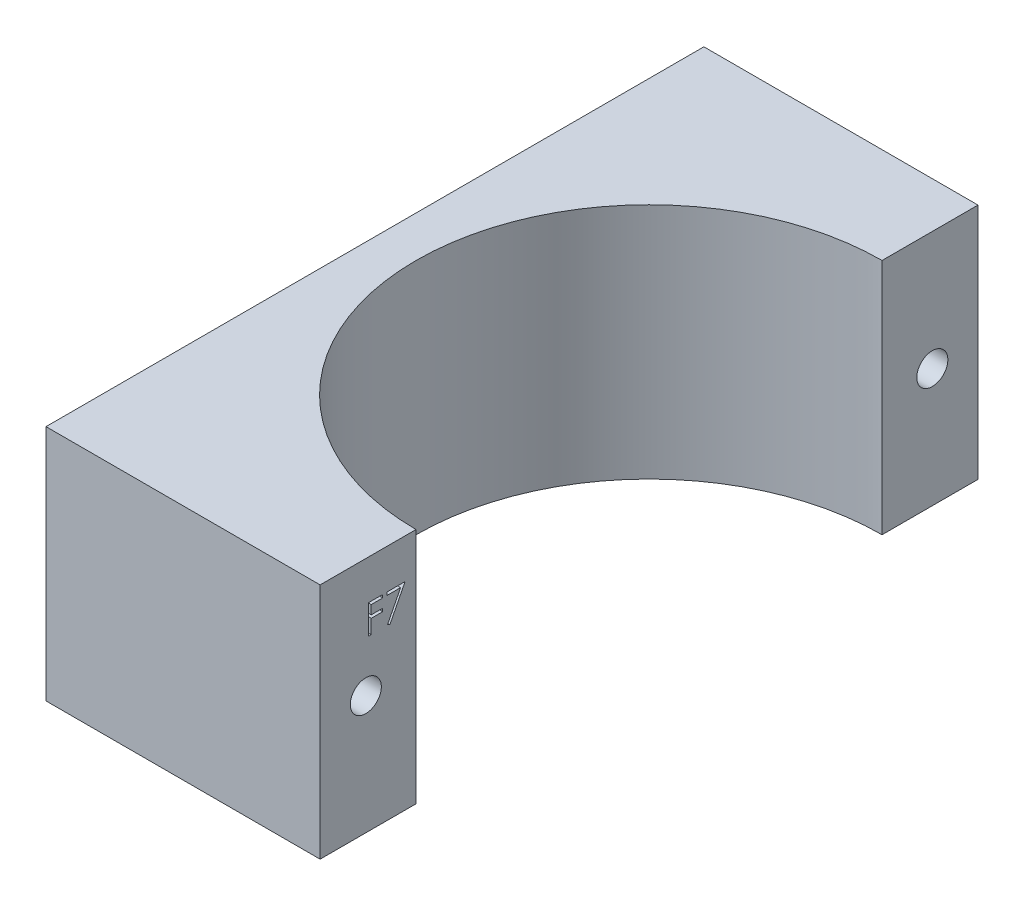
SolidWorks part; units mm, degrees
ref_plane "Front Plane" through (0, 0, 0) normal (0, 0, 1) x (1, 0, 0)
ref_plane "Top Plane" through (0, 0, 0) normal (0, 1, 0) x (1, 0, 0)
ref_plane "Right Plane" through (0, 0, 0) normal (1, 0, 0) x (0, 0, -1)
sketch "Sketch1" plane through (0, 0, 0) normal (0, 1, 0) x (1, 0, 0)
  line L0 (-46.9983, 32.5286) -> (-46.9983, -39.4714)
  line L1 (-46.9983, -39.4714) -> (-16.9983, -39.4714)
  line L2 (-16.9983, -39.4714) -> (-16.9983, -28.9714)
  line L3 (-46.9983, 32.5286) -> (-16.9983, 32.5286)
  line L4 (-16.9983, 32.5286) -> (-16.9983, 22.0286)
  arc A0 (-16.9983, 22.0286) -> (-16.9983, -28.9714) centre (-16.9983, -3.4714) ccw
  dimension "D1" = 72
  dimension "D2" = 30
  dimension "D3" = 30
  dimension "D4" = 10.5
  dimension "D5" = 10.5
extrude "Boss-Extrude1" add sketch "Sketch1" along normal blind 26
sketch "Sketch2" plane through (-16.9983, 0, 0) normal (1, 0, 0) x (0, 0, -1)
  line L0 (-34.4714, 26) -> (-34.4714, 0) construction
  line L1 (-39.4714, 26) -> (-28.9714, 26) construction
  line L2 (-39.4714, 0) -> (-28.9714, 0) construction
  line L3 (27.5286, 26) -> (27.5286, 0) construction
  line L4 (22.0286, 26) -> (32.5286, 26) construction
  line L5 (22.0286, 0) -> (32.5286, 0) construction
  line L6 (-39.4714, 26) -> (-39.4714, 0) construction
  line L7 (32.5286, 26) -> (32.5286, 0) construction
  circle A0 centre (-34.4714, 13) radius 1.7
  circle A1 centre (27.5286, 13) radius 1.7
  dimension "D1" = 5
  dimension "D2" = 5
extrude "Cut-Extrude1" cut sketch "Sketch2" against normal through all
sketch "Sketch3" plane through (-16.9983, 0, 0) normal (1, 0, 0) x (0, 0, -1)
  text T0 "F7"
extrude "Cut-Extrude2" cut sketch "Sketch3" against normal blind 1
